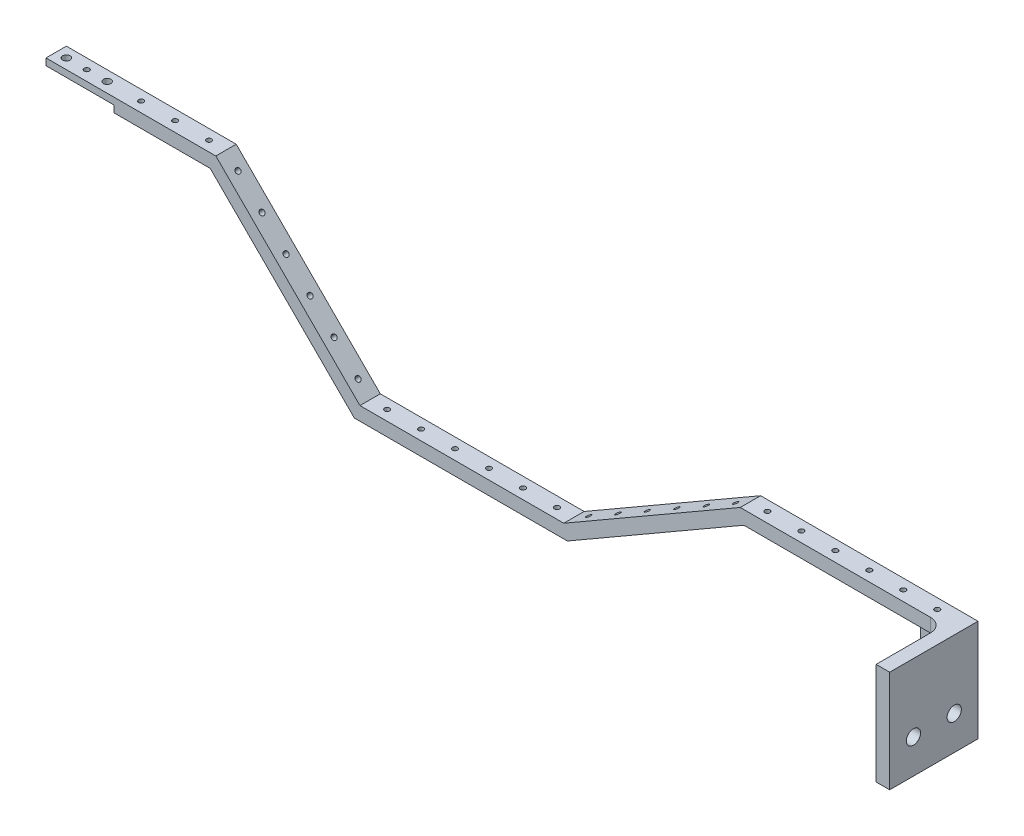
SolidWorks part; units mm, degrees
ref_plane "Front Plane" through (0, 0, 0) normal (0, 0, 1) x (1, 0, 0)
ref_plane "Top Plane" through (0, 0, 0) normal (0, 1, 0) x (1, 0, 0)
ref_plane "Right Plane" through (0, 0, 0) normal (1, 0, 0) x (0, 0, -1)
sketch "Sketch1" plane through (0, 0, 0) normal (0, 0, 1) x (1, 0, 0)
  line L0 (166.5541, -30.9816) -> (166.5541, -0.9816)
  line L1 (166.5541, -0.9816) -> (102.5541, -0.9816)
  line L2 (102.5541, -0.9816) -> (50.5926, -30.9816)
  line L3 (50.5926, -30.9816) -> (-9.4074, -30.9816)
  line L4 (-9.4074, -30.9816) -> (-51.8338, 11.4448)
  line L5 (-51.8338, 11.4448) -> (-101.8338, 11.4448)
  line L6 (166.5541, -30.9816) -> (162.5541, -30.9816)
  line L7 (162.5541, -30.9816) -> (162.5541, -4.9816)
  line L8 (162.5541, -4.9816) -> (103.6259, -4.9816)
  line L9 (103.6259, -4.9816) -> (51.6644, -34.9816)
  line L10 (51.6644, -34.9816) -> (-11.0642, -34.9816)
  line L11 (-11.0642, -34.9816) -> (-53.4906, 7.4448)
  line L12 (-53.4906, 7.4448) -> (-101.8338, 7.4448)
  line L13 (-101.8338, 7.4448) -> (-101.8338, 11.4448)
  dimension "D1" = 30
  dimension "D2" = 64
  dimension "D3" = 60
  dimension "D4" = 150
  dimension "D5" = 60
  dimension "D6" = 60
  dimension "D7" = 50
  dimension "D8" = 135
  dimension "D9" = 4
  dimension "D10" = 4
  dimension "D11" = 4
  dimension "D12" = 4
  dimension "D13" = 4
  dimension "D14" = 4
extrude "Boss-Extrude1" add sketch "Sketch1" along normal blind 6
sketch "Sketch3" plane through (0, 0, 6) normal (0, 0, 1) x (1, 0, 0)
  line L1 (-101.8338, 7.4448) -> (-81.8338, 7.4448)
  line L2 (-101.8338, 7.4448) -> (-101.8338, 9.4448)
  line L3 (-101.8338, 9.4448) -> (-81.8338, 9.4448)
  line L4 (-81.8338, 7.4448) -> (-81.8338, 9.4448)
  dimension "D1" = 2
  dimension "D2" = 20
extrude "Cut-Extrude1" cut sketch "Sketch3" against normal blind 6
sketch "Sketch4" plane through (0, -0.9816, 0) normal (0, 1, 0) x (1, 0, 0)
  line L0 (166.5541, 0) -> (102.5541, 0) construction
  line L1 (102.5541, -6) -> (102.5541, 0) construction
  circle A0 centre (107.5541, -3) radius 0.75
  circle A2 centre (117.5541, -3) radius 0.75
  circle A4 centre (127.5541, -3) radius 0.75
  circle A6 centre (137.5541, -3) radius 0.75
  circle A8 centre (147.5541, -3) radius 0.75
  circle A10 centre (157.5541, -3) radius 0.75
  circle A11 centre (152.5541, -3) radius 0.75 [skipped]
  circle A12 centre (142.5541, -3) radius 0.75 [skipped]
  circle A13 centre (132.5541, -3) radius 0.75 [skipped]
  circle A14 centre (122.5541, -3) radius 0.75 [skipped]
  circle A15 centre (112.5541, -3) radius 0.75 [skipped]
  dimension "D1" = 1.5
  dimension "D2" = 3
  dimension "D3" = 5
  dimension "D4" = 11
extrude "Cut-Extrude2" cut sketch "Sketch4" against normal through all
sketch "Sketch5" plane through (26.0636, -45.1434, 0) normal (-0.5, 0.866, 0) x (0.866, 0.5, 0)
  line L0 (88.3237, 0) -> (28.3237, 0) construction
  line L1 (28.3237, -6) -> (28.3237, 0) construction
  circle A0 centre (33.3237, -3) radius 0.75
  circle A2 centre (43.3237, -3) radius 0.75
  circle A4 centre (53.3237, -3) radius 0.75
  circle A6 centre (63.3237, -3) radius 0.75
  circle A8 centre (73.3237, -3) radius 0.75
  circle A10 centre (83.3237, -3) radius 0.75
  circle A11 centre (78.3237, -3) radius 0.75 [skipped]
  circle A12 centre (68.3237, -3) radius 0.75 [skipped]
  circle A13 centre (58.3237, -3) radius 0.75 [skipped]
  circle A14 centre (48.3237, -3) radius 0.75 [skipped]
  circle A15 centre (38.3237, -3) radius 0.75 [skipped]
  dimension "D1" = 1.5
  dimension "D2" = 3
  dimension "D3" = 5
  dimension "D4" = 11
extrude "Cut-Extrude3" cut sketch "Sketch5" against normal through all
sketch "Sketch6" plane through (0, -30.9816, 0) normal (0, 1, 0) x (1, 0, 0)
  line L0 (50.5926, -6) -> (-9.4074, -6) construction
  line L1 (50.5926, -6) -> (50.5926, 0) construction
  circle A0 centre (45.5926, -3) radius 0.75
  circle A2 centre (35.5926, -3) radius 0.75
  circle A4 centre (25.5926, -3) radius 0.75
  circle A6 centre (15.5926, -3) radius 0.75
  circle A8 centre (5.5926, -3) radius 0.75
  circle A10 centre (-4.4074, -3) radius 0.75
  circle A11 centre (40.5926, -3) radius 0.75 [skipped]
  circle A12 centre (30.5926, -3) radius 0.75 [skipped]
  circle A13 centre (20.5926, -3) radius 0.75 [skipped]
  circle A14 centre (10.5926, -3) radius 0.75 [skipped]
  circle A15 centre (0.5926, -3) radius 0.75 [skipped]
  dimension "D1" = 1.5
  dimension "D2" = 3
  dimension "D3" = 5
  dimension "D4" = 11
extrude "Cut-Extrude4" cut sketch "Sketch6" against normal through all
sketch "Sketch7" plane through (-20.1945, -20.1945, 0) normal (0.7071, 0.7071, 0) x (0, 0, -1)
  line L0 (-6, -15.2552) -> (0, -15.2552) construction
  line L1 (0, -15.2552) -> (0, 44.7448) construction
  circle A0 centre (-3, -10.2552) radius 0.75
  circle A2 centre (-3, -0.2552) radius 0.75
  circle A4 centre (-3, 9.7448) radius 0.75
  circle A6 centre (-3, 19.7448) radius 0.75
  circle A8 centre (-3, 29.7448) radius 0.75
  circle A10 centre (-3, 39.7448) radius 0.75
  circle A11 centre (-3, -5.2552) radius 0.75 [skipped]
  circle A12 centre (-3, 4.7448) radius 0.75 [skipped]
  circle A13 centre (-3, 14.7448) radius 0.75 [skipped]
  circle A14 centre (-3, 24.7448) radius 0.75 [skipped]
  circle A15 centre (-3, 34.7448) radius 0.75 [skipped]
  dimension "D1" = 1.5
  dimension "D2" = 5
  dimension "D3" = 3
  dimension "D4" = 11
extrude "Cut-Extrude5" cut sketch "Sketch7" against normal through all
sketch "Sketch9" plane through (0, 11.4448, 0) normal (0, 1, 0) x (1, 0, 0)
  line L0 (-51.8338, -6) -> (-101.8338, -6) construction
  line L1 (-51.8338, -6) -> (-51.8338, 0) construction
  circle A0 centre (-56.8338, -3) radius 0.75
  circle A1 centre (-66.8338, -3) radius 0.75
  circle A2 centre (-76.8338, -3) radius 0.75
  dimension "D1" = 1.5
  dimension "D2" = 3
  dimension "D3" = 5
  dimension "D4" = 3
extrude "Cut-Extrude6" cut sketch "Sketch9" against normal blind 12
sketch "Sketch10" plane through (0, 9.4448, 0) normal (0, -1, 0) x (1, 0, 0)
  line L0 (-81.8338, 0) -> (-101.8338, 0) construction
  line L1 (-101.8338, 0) -> (-101.8338, 6) construction
  circle A0 centre (-98.8338, 3) radius 1.1
  dimension "D1" = 2.2
  dimension "D2" = 3
  dimension "D3" = 3
extrude "Cut-Extrude7" cut sketch "Sketch10" against normal blind 12
sketch "Sketch11" plane through (0, 9.4448, 0) normal (0, -1, 0) x (1, 0, 0)
  line L0 (-81.8338, 0) -> (-101.8338, 0) construction
  line L1 (-101.8338, 0) -> (-101.8338, 6) construction
  circle A0 centre (-86.8338, 3) radius 1.1
  dimension "D1" = 2.2
  dimension "D2" = 3
  dimension "D3" = 15
extrude "Cut-Extrude8" cut sketch "Sketch11" against normal blind 12
sketch "Sketch12" plane through (0, 9.4448, 0) normal (0, -1, 0) x (1, 0, 0)
  line L0 (-81.8338, 0) -> (-101.8338, 0) construction
  line L1 (-101.8338, 0) -> (-101.8338, 6) construction
  circle A0 centre (-92.8338, 3) radius 0.75
  dimension "D1" = 1.5
  dimension "D2" = 3
  dimension "D3" = 9
extrude "Cut-Extrude9" cut sketch "Sketch12" against normal blind 12
sketch "Sketch15" plane through (166.5541, 0, 0) normal (1, 0, 0) x (0, 0, -1)
  line L1 (-6, -0.9816) -> (-26, -0.9816)
  line L2 (-6, -0.9816) -> (-6, -30.9816)
  line L3 (-6, -30.9816) -> (-26, -30.9816)
  line L4 (-26, -0.9816) -> (-26, -30.9816)
  dimension "D1" = 20
extrude "Boss-Extrude4" add sketch "Sketch15" against normal blind 4
fillet "Fillet4" radius 4 2 edges at (162.5541, -2.9816, 6) (162.5541, -4.9816, 3)
sketch "Sketch16" plane through (0, 0, 0) normal (0, 0, -1) x (-1, 0, 0)
  line L1 (-166.5541, -0.9816) -> (-151.5541, -0.9816)
  line L2 (-166.5541, -0.9816) -> (-166.5541, -30.9816)
  line L3 (-166.5541, -30.9816) -> (-151.5541, -30.9816)
  line L4 (-151.5541, -0.9816) -> (-151.5541, -30.9816)
  dimension "D1" = 15
extrude "Boss-Extrude5" add sketch "Sketch16" against normal blind 2
fillet "Fillet5" radius 3 3 edges at (162.5541, -19.9816, 2) (161.3826, -6.1531, 2) (155.0541, -4.9816, 2)
fillet "Fillet6" radius 3 1 edges at (151.5541, -4.9816, 2.5)
sketch "Sketch17" plane through (166.5541, 0, 0) normal (1, 0, 0) x (0, 0, -1)
  line L0 (0, -30.9816) -> (0, -0.9816) construction
  line L1 (-26, -0.9816) -> (-26, -30.9816) construction
  line L2 (-26, -30.9816) -> (0, -30.9816) construction
  circle A0 centre (-19, -20.9816) radius 2.1
  circle A1 centre (-7, -20.9816) radius 2.1
  dimension "D1" = 4.2
  dimension "D2" = 4.2
  dimension "D3" = 7
  dimension "D4" = 7
  dimension "D5" = 10
  dimension "D6" = 10
extrude "Cut-Extrude12" cut sketch "Sketch17" against normal blind 4
